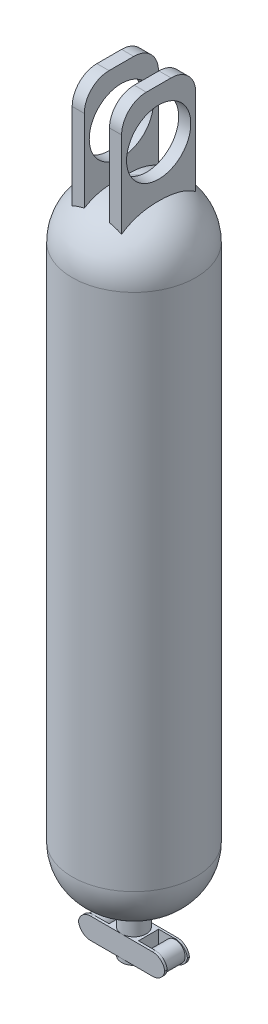
SolidWorks part; units mm, degrees
ref_plane "Front Plane" through (0, 0, 0) normal (0, 0, 1) x (1, 0, 0)
ref_plane "Top Plane" through (0, 0, 0) normal (0, 1, 0) x (1, 0, 0)
ref_plane "Right Plane" through (0, 0, 0) normal (1, 0, 0) x (0, 0, -1)
sketch "Sketch1" plane through (0, 0, 0) normal (0, 1, 0) x (1, 0, 0)
  circle A0 centre (0, 0) radius 2.5
  dimension "D1" = 5
extrude "Boss-Extrude1" add sketch "Sketch1" along normal blind 25
sketch "Sketch2" plane through (0, 25, 0) normal (0, 1, 0) x (1, 0, 0)
  line L0 (-0.5, 1) -> (-0.5, -1)
  line L1 (1, 1.5) -> (-1, 1.5)
  line L2 (1, 1.5) -> (1, -1.5)
  line L3 (1, -1.5) -> (-1, -1.5)
  line L4 (-1, 1.5) -> (-1, -1.5)
  line L5 (1, 1.5) -> (-1, -1.5) construction
  line L6 (1, -1.5) -> (-1, 1.5) construction
  line L7 (0.5, -1) -> (-0.5, -1)
  line L8 (0.5, 1) -> (0.5, -1)
  line L9 (0.5, 1) -> (-0.5, 1)
  point P0 (0, 0)
  dimension "D1" = 2
  dimension "D2" = 3
  dimension "D3" = 0.5
extrude "Boss-Extrude2" add sketch "Sketch2" along normal blind 4
sketch "Sketch3" plane through (0, 29, 0) normal (0, 1, 0) x (1, 0, 0)
  line L1 (0.5095, 1.6146) -> (-0.5095, 1.6146)
  line L2 (0.5095, 1.6146) -> (0.5095, -1.6146)
  line L3 (0.5095, -1.6146) -> (-0.5095, -1.6146)
  line L4 (-0.5095, 1.6146) -> (-0.5095, -1.6146)
  line L5 (0.5095, 1.6146) -> (-0.5095, -1.6146) construction
  line L6 (0.5095, -1.6146) -> (-0.5095, 1.6146) construction
  point P0 (0, 0)
extrude "Cut-Extrude1" cut sketch "Sketch3" against normal blind 4
sketch "Sketch4" plane through (-1, 0, 0) normal (-1, 0, 0) x (0, 0, 1)
  line L0 (0, 29) -> (0, 27)
  line L1 (-1.5, 29) -> (1.5, 29) construction
  circle A0 centre (0, 27) radius 1.3
extrude "Cut-Extrude2" cut sketch "Sketch4" against normal blind 4 contours A0 region at (-1, 26.1068, -0.8932)
fillet "Fillet1" radius 1 4 edges at (0.7548, 29, 1.5) (0.7548, 29, -1.5) (-0.7548, 29, -1.5) (-0.7548, 29, 1.5)
fillet "Fillet2" radius 2 2 edges at (0, 25, 2.5) (0, 0, 2.5)
sketch "Sketch5" plane through (0, 0, 0) normal (0, 1, 0) x (1, 0, 0)
  circle A0 centre (0, 0) radius 0.5
extrude "Boss-Extrude3" add sketch "Sketch5" against normal blind 2
sketch "Sketch6" plane through (0, 0, 0) normal (0, 0, 1) x (1, 0, 0)
  line L1 (-1.7518, -0.9985) -> (1.7518, -0.9985)
  line L2 (-1.7518, -0.9985) -> (-1.7518, -1.8573)
  line L3 (-1.7518, -1.8573) -> (1.7518, -1.8573)
  line L4 (1.7518, -0.9985) -> (1.7518, -1.8573)
  line L5 (-1.7518, -0.9985) -> (1.7518, -1.8573) construction
  line L6 (-1.7518, -1.8573) -> (1.7518, -0.9985) construction
  point P0 (0, -1.4279)
extrude "Boss-Extrude4" add sketch "Sketch6" along normal mid plane 1
fillet "Fillet3" radius 0.5 4 edges at (1.7518, -0.9985, 0) (1.7518, -1.8573, 0) (-1.7518, -0.9985, 0) (-1.7518, -1.8573, 0)
sketch "Sketch7" plane through (0, -1.8573, 0) normal (0, -1, 0) x (1, 0, 0)
  line L2 (-0.9185, -0.4175) -> (-0.9185, 0.3979)
  line L3 (-0.9185, 0.3979) -> (-0.6093, 0.3979)
  line L4 (-0.6093, 0.3979) -> (-0.6093, -0.4175)
  line L5 (-0.6093, -0.4175) -> (-0.9185, -0.4175)
extrude "Cut-Extrude6" cut sketch "Sketch7" against normal blind 1
pattern_linear "LPattern1" count 2 spacing 1.5 along (1, 0, 0) of "Cut-Extrude6"
fillet "Fillet4" radius 0.5 4 edges at (0.8907, -0.9985, -0.0098) (0.8907, -1.8573, -0.0098) (-0.9185, -0.9985, -0.0098) (-0.9185, -1.8573, -0.0098)
sketch "Sketch10" plane through (0, -1.8573, 0) normal (0, -1, 0) x (1, 0, 0)
  line L0 (-0.9236, 0.3979) -> (-1.7848, 0.3979)
  line L1 (-1.7848, 0.3979) -> (-1.7848, -0.4175)
  line L2 (-1.7848, -0.4175) -> (-0.877, -0.4175)
  line L3 (-1.2518, -0.4175) -> (-0.6093, -0.4175) construction
  line L4 (-0.877, -0.4175) -> (-0.877, 0.3979)
  line L5 (-0.6093, 0.3979) -> (-1.2518, 0.3979) construction
  line L6 (-0.877, 0.3979) -> (-0.9236, 0.3979)
extrude "Cut-Extrude8" cut sketch "Sketch10" against normal blind 1
sketch "Sketch11" plane through (0, -1.8573, 0) normal (0, -1, 0) x (-1, 0, 0)
  line L0 (-0.7417, -0.3979) -> (-1.8581, -0.3979)
  line L1 (-1.2518, -0.3979) -> (-0.5815, -0.3979) construction
  line L2 (-1.8581, -0.3979) -> (-1.8581, 0.4175)
  line L3 (-1.8581, 0.4175) -> (-0.7833, 0.4175)
  line L4 (-0.5815, 0.4175) -> (-1.2518, 0.4175) construction
  line L5 (-0.7833, 0.4175) -> (-0.7417, -0.3979)
extrude "Cut-Extrude9" cut sketch "Sketch11" against normal blind 1
sketch "Sketch12" plane through (0, 0, 0.5) normal (0, 0, 1) x (1, 0, 0)
  circle A0 centre (-1.2518, -1.4279) radius 0.4
extrude "Boss-Extrude5" add sketch "Sketch12" against normal blind 1
sketch "Sketch13" plane through (0, 0, 0.5) normal (0, 0, 1) x (1, 0, 0)
  circle A0 centre (1.2518, -1.4279) radius 0.4
extrude "Boss-Extrude6" add sketch "Sketch13" against normal blind 1
